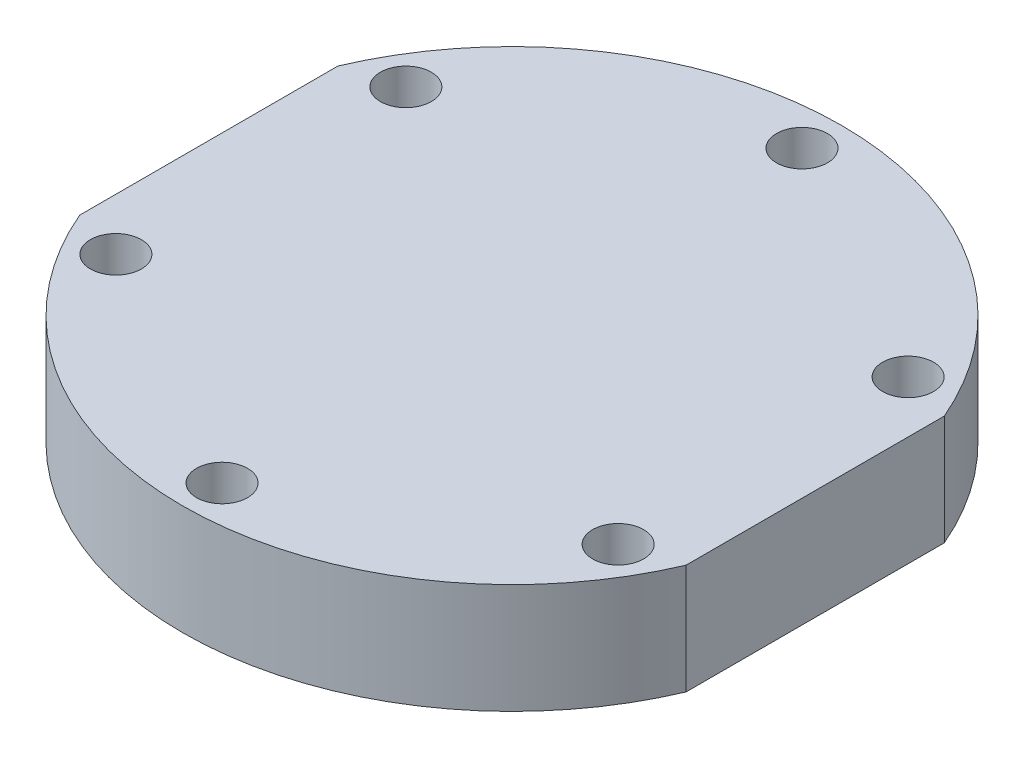
SolidWorks part; units mm, degrees
material "Copper"
ref_plane "Front Plane" through (0, 0, 0) normal (0, 0, 1) x (1, 0, 0)
ref_plane "Top Plane" through (0, 0, 0) normal (0, 1, 0) x (1, 0, 0)
ref_plane "Right Plane" through (0, 0, 0) normal (1, 0, 0) x (0, 0, -1)
ref_axis "Y Axis" through (0, 6.6675, 0) along (0, -1, 0)
sketch "outer" plane through (0, 0, 0) normal (0, 1, 0) x (1, 0, 0)
  circle A0 centre (0, 0) radius 19.05
  dimension "D1" = 38.1
extrude "Body" add sketch "outer" along normal blind 6.35
sketch "inner" plane through (0, 0, 0) normal (0, 1, 0) x (1, 0, 0)
  circle A0 centre (0, 0) radius 11.938
  dimension "D1" = 23.876
extrude "Pocket" cut sketch "inner" along normal blind 3.81
sketch "Screw Position" plane through (0, 0, 0) normal (0, 1, 0) x (1, 0, 0)
  point P0 (0, 16.764)
  dimension "D1" = 16.764
hole_wizard "#4 Clearance Hole1" positions "Sketch7" profile "Sketch8" hole size "#4" standard "ANSI Inch" end condition through all
sketch "Sketch7" plane through (0, 6.35, 0) normal (0, 1, 0) x (1, 0, 0)
  point P0 (0, 16.764)
sketch "Sketch8" plane through (0, 6.35, -16.764) normal (1, 0, 0) x (0, 0, 1)
  line L0 (0, 0) -> (0, 6.35)
  line L1 (0, 6.35) -> (1.4732, 6.35)
  line L2 (1.4732, 6.35) -> (1.4732, 0)
  line L5 (1.4732, 0) -> (0, 0)
  line L11 (0, -6.35) -> (0, 107.95) construction
  dimension "Thru Hole Dia." = 2.9464
  dimension "Thru Hole Depth" = 6.35
pattern_circular "Screw Holes" count 6 over 360 about axis through (0, 6.6675, 0) along (0, -1, 0) of "#4 Clearance Hole1"
sketch "Post Sketch" plane through (0, 0, 0) normal (0, 1, 0) x (1, 0, 0)
  circle A1 centre (5.3033, -5.3033) radius 1.2065
  point P0 (0, -7)
  point P1 (5.3033, -5.3033)
  dimension "D4" = 2.413
  dimension "D1" = 7
extrude "Post" add sketch "Post Sketch" against normal blind 4.572 from surface starting at face at (0, 3.81, 11.938)
pattern_circular "Posts" count 4 over 360 about axis through (0, 6.6675, 0) along (0, -1, 0) of "Post"
sketch "Cut Sketch" plane through (0, 0, 0) normal (0, 1, 0) x (1, 0, 0)
  line L0 (-17.526, -19.05) -> (-20.574, -19.05)
  line L1 (17.526, 19.05) -> (20.574, 19.05)
  line L2 (17.526, 19.05) -> (17.526, -19.05)
  line L3 (17.526, -19.05) -> (20.574, -19.05)
  line L4 (20.574, 19.05) -> (20.574, -19.05)
  line L5 (17.526, 19.05) -> (20.574, -19.05) construction
  line L6 (17.526, -19.05) -> (20.574, 19.05) construction
  line L7 (-17.526, -19.05) -> (-17.526, 19.05)
  line L8 (-17.526, 19.05) -> (-20.574, 19.05)
  line L9 (-20.574, -19.05) -> (-20.574, 19.05)
  line L10 (-17.526, -19.05) -> (-20.574, 19.05) construction
  line L11 (-17.526, 19.05) -> (-20.574, -19.05) construction
  circle A0 centre (0, 0) radius 19.05 construction
  point P0 (19.05, 0)
  point P9 (-19.05, 0)
  point P14 (0, 0)
  dimension "D1" = 38.1
  dimension "D2" = 3.048
  dimension "D3" = 2
extrude "Cut-Extrude1" cut sketch "Cut Sketch" against normal through all and the other way through all
equation "\"outer_d\"= 3 / 2in"
equation "\"top_h\"= 1 / 4in"
equation "\"screw_r\"= 0.66in"
equation "\"inner_d\"= 0.94in"
equation "\"inner_h\"= 150mil"
equation "\"D1@outer\" = \"outer_d\""
equation "\"D1@Body\" = \"top_h\""
equation "\"D1@inner\"=\"inner_d\""
equation "\"D1@Pocket\" = \"inner_h\""
equation "\"D1@Screw Position\"=\"screw_r\""
equation "\"post_r1\"= 7mm"
equation "\"post_r2\"= 7.5mm"
equation "\"post_bottom_h\"= 0.03in"
equation "\"D1@Post Sketch\" = \"post_r1\""
equation "\"D2@Post Sketch\" = \"post_r2\""
equation "\"post_d\"= 0.095in"
equation "\"D4@Post Sketch\"=\"post_d\""
equation "\"D1@Post\" = \"inner_h\" + \"post_bottom_h\""
equation "\"cut\"= 0.06in"
equation "\"D1@Cut Sketch\"=\"outer_d\""
equation "\"D2@Cut Sketch\"=2 * \"cut\""
